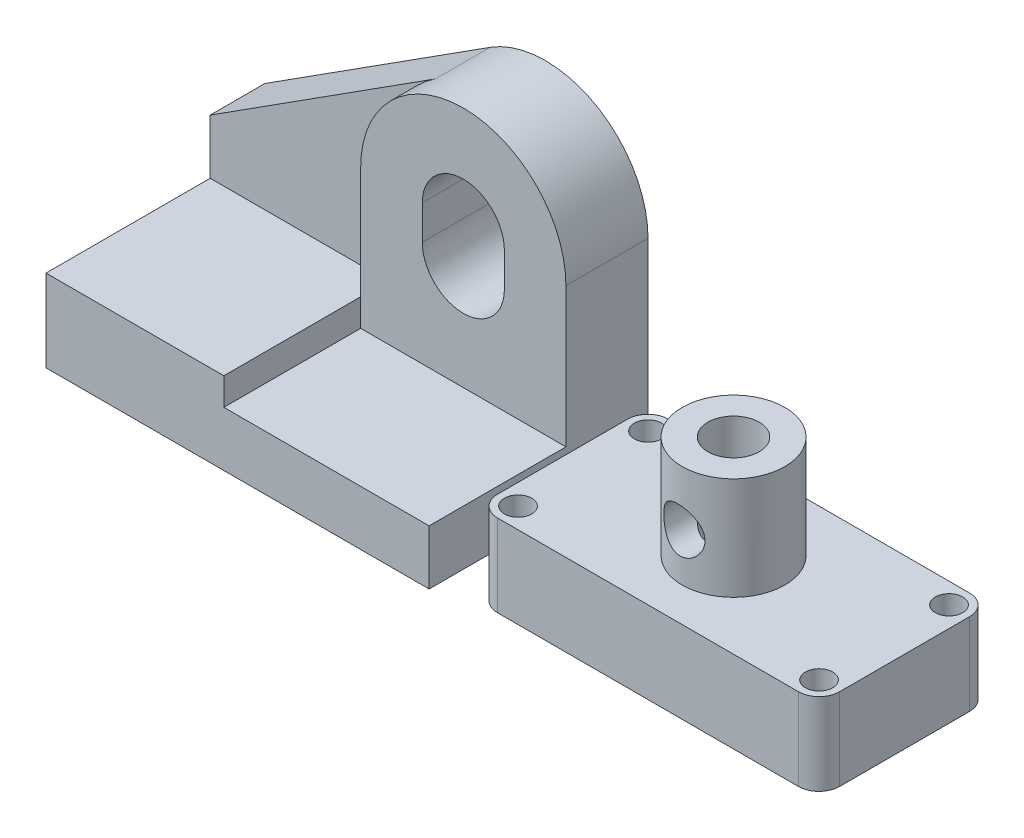
SolidWorks part; units mm, degrees
ref_plane "前视基准面" through (0, 0, 0) normal (0, 0, 1) x (1, 0, 0)
ref_plane "上视基准面" through (0, 0, 0) normal (0, 1, 0) x (1, 0, 0)
ref_plane "右视基准面" through (0, 0, 0) normal (1, 0, 0) x (0, 0, -1)
other "Configuration Table"
sketch "草图1" plane through (0, 0, 0) normal (0, 0, 1) x (1, 0, 0)
  line L0 (0, 0) -> (56, 0)
  line L1 (56, 0) -> (56, 28.3982)
  line L2 (0, 0) -> (0, 20)
  line L3 (26, 8) -> (26, 28.3982)
  line L4 (0, 12) -> (26, 12)
  line L5 (26, 8) -> (56, 8)
  line L6 (0, 20) -> (32.9231, 41.038)
  line L7 (41, 28.3982) -> (41, 23.3982) construction
  line L8 (47, 28.3982) -> (47, 23.3982)
  line L9 (35, 28.3982) -> (35, 23.3982)
  arc A0 (56, 28.3982) -> (26, 28.3982) centre (41, 28.3982) ccw
  arc A1 (47, 28.3982) -> (35, 28.3982) centre (41, 28.3982) ccw
  arc A2 (35, 23.3982) -> (47, 23.3982) centre (41, 23.3982) ccw
  point P5 (41, 25.8982)
  dimension "D1" = 56
  dimension "D5" = 6
  dimension "D7" = 15
  dimension "D2" = 20
  dimension "D3" = 12
  dimension "D4" = 8
  dimension "D6" = 5
extrude "凸台-拉伸1" add sketch "草图1" along normal blind 32 contours L5 L3 L4 L2 L0 L1 region at (25.1739, 5.1304, 0)
extrude "凸台-拉伸2" add sketch "草图1<3>" along normal blind 8 contours A0 L6 L2 L4 L3 region at (15.503, 21.2201, 0)
sketch "草图1<3>" plane through (0, 0, 0) normal (0, 0, 1) x (1, 0, 0) same geometry as "草图1"
extrude "凸台-拉伸3" add sketch "草图1<4>" along normal blind 12 contours L1 A0 L3 L5 A2 L9 A1 L8 region at (41, 8.464, 0)
sketch "草图1<4>" plane through (0, 0, 0) normal (0, 0, 1) x (1, 0, 0) same geometry as "草图1"
sketch "草图2" plane through (0, 0, 0) normal (0, 1, 0) x (1, 0, 0)
  line L0 (56, -32) -> (56, -12) construction
  line L1 (64, -5) -> (108, -5)
  line L2 (61, -8) -> (61, -27)
  line L3 (64, -30) -> (108, -30)
  line L4 (111, -8) -> (111, -27)
  line L5 (61, -5) -> (111, -30) construction
  line L6 (61, -30) -> (111, -5) construction
  line L7 (0, 0) -> (56, 0) construction
  arc A0 (108, -5) -> (111, -8) centre (108, -8) cw
  arc A1 (61, -27) -> (64, -30) centre (64, -27) ccw
  arc A2 (64, -5) -> (61, -8) centre (64, -8) ccw
  arc A3 (108, -30) -> (111, -27) centre (108, -27) ccw
  circle A4 centre (64, -8) radius 2
  circle A5 centre (64, -27) radius 2
  circle A7 centre (108, -8) radius 2
  circle A8 centre (108, -27) radius 2
  point P0 (86, -17.5)
  dimension "D5" = 3
  dimension "D6" = 4
  dimension "D1" = 50
  dimension "D2" = 25
  dimension "D3" = 5
  dimension "D4" = 5
extrude "凸台-拉伸4" add sketch "草图2" along normal blind 12 separate body
sketch "草图3" plane through (0, 12, 0) normal (0, 1, 0) x (1, 0, 0)
  line L0 (86, -5) -> (86, -30) construction
  line L1 (111, -27) -> (111, -8) construction
  line L2 (108, -5) -> (64, -5) construction
  line L3 (61, -17.5) -> (111, -17.5) construction
  line L4 (61, -8) -> (61, -27) construction
  line L5 (64, -30) -> (108, -30) construction
  circle A0 centre (86, -17.5) radius 7.5
  circle A1 centre (86, -17.5) radius 3.75
  point P15 (0, 0)
  point P16 (0, 0)
  point P17 (0, 0)
  dimension "D1" = 15
  dimension "D2" = 7.5
extrude "凸台-拉伸5" add sketch "草图3" along normal blind 15
extrude "切除-拉伸2" cut sketch "草图3<5>" against normal blind 15 contours A1
sketch "草图3<5>" plane through (0, 12, 0) normal (0, 1, 0) x (1, 0, 0) same geometry as "草图3"
ref_plane "基准面2" through (0, 0, 17.5) normal (0, 0, 1) x (1, 0, 0)
sketch "草图7" plane through (0, 0, 17.5) normal (0, 0, 1) x (1, 0, 0)
  circle A0 centre (85.5858, 18.7379) radius 3.2108
extrude "切除-拉伸3" cut sketch "草图7" against normal blind 15 and the other way blind 15
